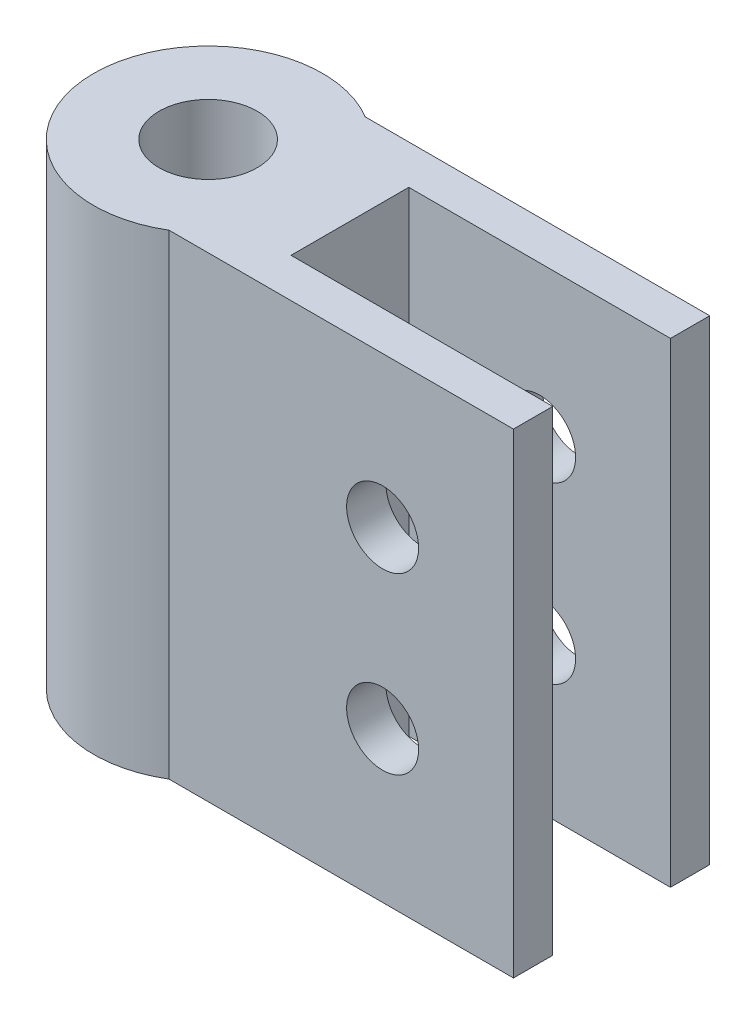
SolidWorks part; units mm, degrees
ref_plane "前视基准面" through (0, 0, 0) normal (0, 0, 1) x (1, 0, 0)
ref_plane "上视基准面" through (0, 0, 0) normal (0, 1, 0) x (1, 0, 0)
ref_plane "右视基准面" through (0, 0, 0) normal (1, 0, 0) x (0, 0, -1)
sketch "草图1" plane through (0, 0, 0) normal (0, 1, 0) x (1, 0, 0)
  circle A0 centre (0, 0) radius 2.25
  circle A1 centre (0, 0) radius 5.25
  dimension "D1" = 4.5
  dimension "D2" = 3
extrude "凸台-拉伸1" add sketch "草图1" along normal blind 21.8
sketch "草图2" plane through (0, 21.8, 0) normal (0, 1, 0) x (1, 0, 0)
  line L1 (18.5, -4.5) -> (2.5, -4.5)
  line L2 (18.5, -4.5) -> (18.5, 4.5)
  line L3 (18.5, 4.5) -> (2.5, 4.5)
  line L4 (2.5, -4.5) -> (2.5, 4.5)
  line L5 (18.5, -4.5) -> (2.5, 4.5) construction
  line L6 (18.5, 4.5) -> (2.5, -4.5) construction
  point P0 (10.5, 0)
  dimension "D1" = 10.5
  dimension "D2" = 16
  dimension "D3" = 9
extrude "凸台-拉伸2" add sketch "草图2" against normal up to surface (21.8 mm away) up to face at (0, 0, 5.25)
sketch "草图3" plane through (0, 21.8, 0) normal (0, 1, 0) x (1, 0, 0)
  line L0 (18.5, -4.5) -> (18.5, 4.5) construction
  line L1 (6.5, -2.7) -> (18.5, -2.7)
  line L2 (6.5, -2.7) -> (6.5, 2.7)
  line L3 (6.5, 2.7) -> (18.5, 2.7)
  line L4 (18.5, -2.7) -> (18.5, 2.7)
  line L5 (6.5, -2.7) -> (18.5, 2.7) construction
  line L6 (6.5, 2.7) -> (18.5, -2.7) construction
  point P0 (12.5, 0)
  dimension "D1" = 5.4
  dimension "D2" = 12
extrude "切除-拉伸1" cut sketch "草图3" against normal blind 22
sketch "草图4" plane through (0, 0, 4.5) normal (0, 0, 1) x (1, 0, 0)
  line L0 (6.5, 0) -> (6.5, 21.8) construction
  line L1 (6.5, 0) -> (6.5, 21.8) construction
  line L2 (2.7042, 21.8) -> (18.5, 21.8) construction
  circle A0 centre (12.5, 14.9) radius 1.65
  circle A1 centre (12.5, 6.9) radius 1.65
  dimension "D1" = 3.3
  dimension "D2" = 3.3
  dimension "D3" = 6.9
  dimension "D4" = 6
  dimension "D5" = 8
extrude "切除-拉伸2" cut sketch "草图4" against normal blind 22
